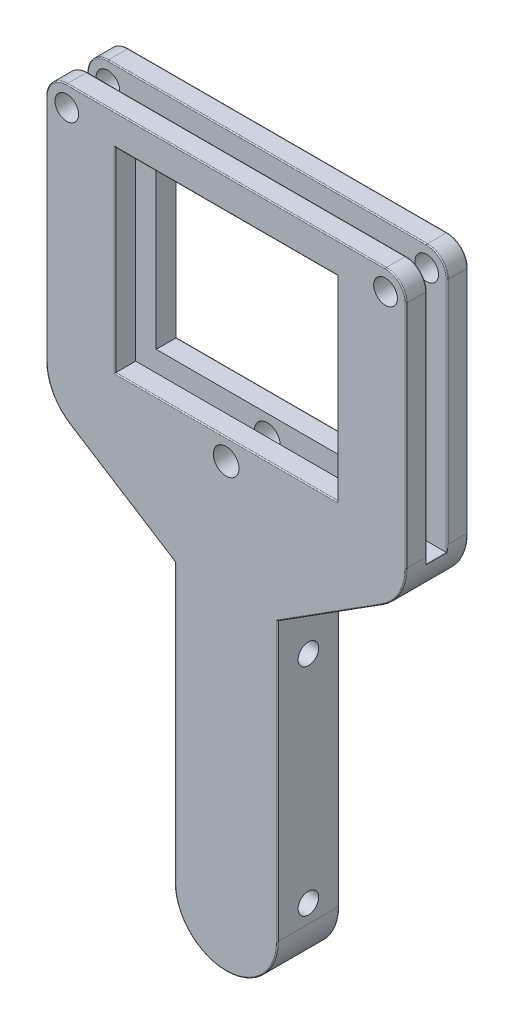
SolidWorks part; units mm, degrees
ref_plane "Front Plane" through (0, 0, 0) normal (0, 0, 1) x (1, 0, 0)
ref_plane "Top Plane" through (0, 0, 0) normal (0, 1, 0) x (1, 0, 0)
ref_plane "Right Plane" through (0, 0, 0) normal (1, 0, 0) x (0, 0, -1)
sketch "Sketch2" plane through (0, 0, 0) normal (0, 0, 1) x (1, 0, 0)
  line L0 (0, 19.269) -> (0, -20.775) construction
  line L1 (-22.186, 0) -> (24.4048, 0) construction
  line L3 (-22.225, -22.225) -> (22.225, -22.225)
  line L4 (-22.225, -22.225) -> (-22.225, 22.225)
  line L5 (-22.225, 22.225) -> (22.225, 22.225)
  line L6 (22.225, -22.225) -> (22.225, 22.225)
  line L7 (-22.225, -22.225) -> (22.225, 22.225) construction
  line L8 (-22.225, 22.225) -> (22.225, -22.225) construction
  point P5 (0, 0)
  dimension "D1" = 44.45
  dimension "D2" = 44.45
extrude "Boss-Extrude1" add sketch "Sketch2" along normal blind 7.62
sketch "Sketch3" plane through (0, 0, 7.62) normal (0, 0, 1) x (1, 0, 0)
  line L0 (22.225, 22.225) -> (-22.225, 22.225) construction
  line L1 (-13.716, -5.715) -> (13.716, -5.715)
  line L2 (-13.716, -5.715) -> (-13.716, 18.415)
  line L3 (-13.716, 18.415) -> (13.716, 18.415)
  line L4 (13.716, -5.715) -> (13.716, 18.415)
  point P0 (0, 0)
  point P8 (0, -5.715)
  dimension "D1" = 3.81
  dimension "D2" = 27.432
  dimension "D3" = 24.13
extrude "Cut-Extrude1" cut sketch "Sketch3" against normal blind 7.62
sketch "Sketch4" plane through (22.225, 0, 0) normal (1, 0, 0) x (0, 0, -1)
  line L0 (-7.62, 22.225) -> (0, 22.225) construction
  line L1 (-5.08, 22.225) -> (-2.54, 22.225)
  line L2 (-5.08, 22.225) -> (-5.08, -9.525)
  line L3 (-5.08, -9.525) -> (-2.54, -9.525)
  line L4 (-2.54, 22.225) -> (-2.54, -9.525)
  line L6 (-7.62, -22.225) -> (-7.62, 22.225) construction
  line L7 (0, -22.225) -> (0, 22.225) construction
  dimension "D1" = 2.54
  dimension "D2" = 2.54
  dimension "D3" = 31.75
extrude "Cut-Extrude2" cut sketch "Sketch4" against normal blind 44.45
sketch "Sketch5" plane through (0, 0, 7.62) normal (0, 0, 1) x (1, 0, 0)
  line L2 (22.225, 22.225) -> (-22.225, 22.225) construction
  line L3 (-22.225, 22.225) -> (-22.225, -22.225) construction
  line L6 (22.225, -22.225) -> (22.225, 22.225) construction
  circle A3 centre (19.685, 19.685) radius 1.4605
  circle A4 centre (-19.685, 19.685) radius 1.4605
  circle A5 centre (0, -8.2887) radius 1.5875
  dimension "D1" = 3.175
  dimension "D2" = 2.921
  dimension "D3" = 2.921
  dimension "D4" = 2.54
  dimension "D5" = 2.54
  dimension "D6" = 2.54
  dimension "D7" = 2.54
extrude "Cut-Extrude3" cut sketch "Sketch5" against normal blind 7.62
sketch "Sketch7" plane through (0, -22.225, 0) normal (0, -1, 0) x (1, 0, 0)
  line L1 (-22.225, 0) -> (22.225, 0)
  line L2 (-22.225, 0) -> (-22.225, 7.62)
  line L3 (-22.225, 7.62) -> (22.225, 7.62)
  line L4 (22.225, 0) -> (22.225, 7.62)
sketch "Sketch8" plane through (0, 0, 0) normal (0, 0, -1) x (-1, 0, 0)
  line L1 (-22.225, -22.225) -> (-22.225, 22.225) construction
  line L4 (22.225, 22.225) -> (22.225, -22.225) construction
  line L6 (-22.225, -12.1541) -> (-22.225, -25.1613)
  line L7 (-22.225, -25.1613) -> (22.225, -25.1613)
  line L8 (22.225, -25.1613) -> (22.225, -12.1541)
  line L9 (-22.225, -12.1541) -> (-6.35, -22.225)
  line L10 (22.225, -22.225) -> (-22.225, -22.225) construction
  line L11 (22.225, -12.1541) -> (6.35, -22.225)
  line L12 (6.35, -22.225) -> (-6.35, -22.225)
  line L13 (22.225, -22.225) -> (-22.225, -22.225) construction
  point P12 (-5.7026, -22.225)
  point P15 (6.8151, -22.225)
  dimension "D1" = 15.875
  dimension "D2" = 15.875
extrude "Cut-Extrude4" cut sketch "Sketch8" against normal blind 7.62
sketch "Sketch10" plane through (0, -22.225, 0) normal (0, -1, 0) x (1, 0, 0)
  line L1 (-6.35, 7.62) -> (6.35, 7.62)
  line L2 (-6.35, 7.62) -> (-6.35, 0)
  line L3 (-6.35, 0) -> (6.35, 0)
  line L4 (6.35, 7.62) -> (6.35, 0)
extrude "Boss-Extrude2" add sketch "Sketch10" along normal blind 40.64
fillet "Fillet2" radius 0.127 33 edges at (0, 22.225, 7.62) (0, -62.865, 7.62) (22.225, 6.35, 5.08) (22.225, -9.525, 3.81) (22.225, 6.35, 2.54) (22.225, 5.0355, 7.62) (14.2875, -17.1895, 7.62) (6.35, -42.545, 7.62) (-14.2875, -17.1895, 7.62) (0, -5.715, 0) (-13.716, 6.35, 0) (0, 18.415, 0) (13.716, 6.35, 0) (22.225, 5.0355, 0) (-14.2875, -17.1895, 0) (0, -62.865, 0) (6.35, -42.545, 0) (14.2875, -17.1895, 0) (-6.35, -42.545, 7.62) (-6.35, -42.545, 0) (-22.225, 6.35, 2.54) (-22.225, -9.525, 3.81) (-22.225, 6.35, 5.08) (-22.225, 5.0355, 7.62) (-22.225, 5.0355, 0) (0, 22.225, 0) (0, 22.225, 2.54) (0, 22.225, 5.08) (0, 18.415, 7.62) (13.716, 6.35, 7.62) (0, -5.715, 7.62) (-13.716, 6.35, 7.62) (0, 18.415, 2.54)
fillet "Fillet3" radius 2.54 12 edges at (22.1878, 22.1878, 5.1172) (22.1878, 22.1878, 7.5828) (22.1878, 22.1878, 0.0372) (22.1878, 22.1878, 2.5028) (-22.1878, 22.1878, 5.1172) (-22.1878, 22.1878, 7.5828) (-22.1878, 22.1878, 0.0372) (-22.1878, 22.1878, 2.5028) (-22.225, 22.225, 1.27) (-22.225, 22.225, 6.35) (22.225, 22.225, 1.27) (22.225, 22.225, 6.35)
fillet "Fillet4" radius 6.35 6 edges at (22.1878, -12.1336, 0.0372) (22.1878, -12.1336, 7.5828) (-22.1878, -12.1336, 0.0372) (-22.1878, -12.1336, 7.5828) (-22.225, -12.1541, 3.81) (22.225, -12.1541, 3.81)
fillet "Fillet5" radius 6.35 4 edges at (-6.3128, -62.8278, 0.0372) (-6.3128, -62.8278, 7.5828) (-6.35, -62.865, 3.81) (6.35, -62.865, 3.81)
sketch "Sketch11" plane through (-6.35, 0, 0) normal (-1, 0, 0) x (0, 0, 1)
  line L0 (3.81, -62.865) -> (3.81, -14.0245) construction
  line L1 (7.493, -62.865) -> (0.127, -62.865) construction
  line L2 (7.493, -14.0245) -> (0.127, -14.0245) construction
  line L3 (3.81, -14.0245) -> (3.81, -38.4448) construction
  line L4 (3.81, -38.4448) -> (-20.509, -38.4448) construction
  line L5 (-20.509, -38.4448) -> (25.268, -38.4448) construction
  line L6 (7.493, -22.225) -> (0.127, -22.225) construction
  circle A0 centre (3.81, -54.2797) radius 1.27
  circle A1 centre (3.81, -27.6097) radius 1.27
  point P13 (3.81, -53.3964)
  point P14 (3.81, -54.2797)
  dimension "D1" = 2.54
  dimension "D2" = 2.54
  dimension "D3" = 26.67
  dimension "D4" = 5.3847
extrude "Cut-Extrude5" cut sketch "Sketch11" against normal blind 12.7
